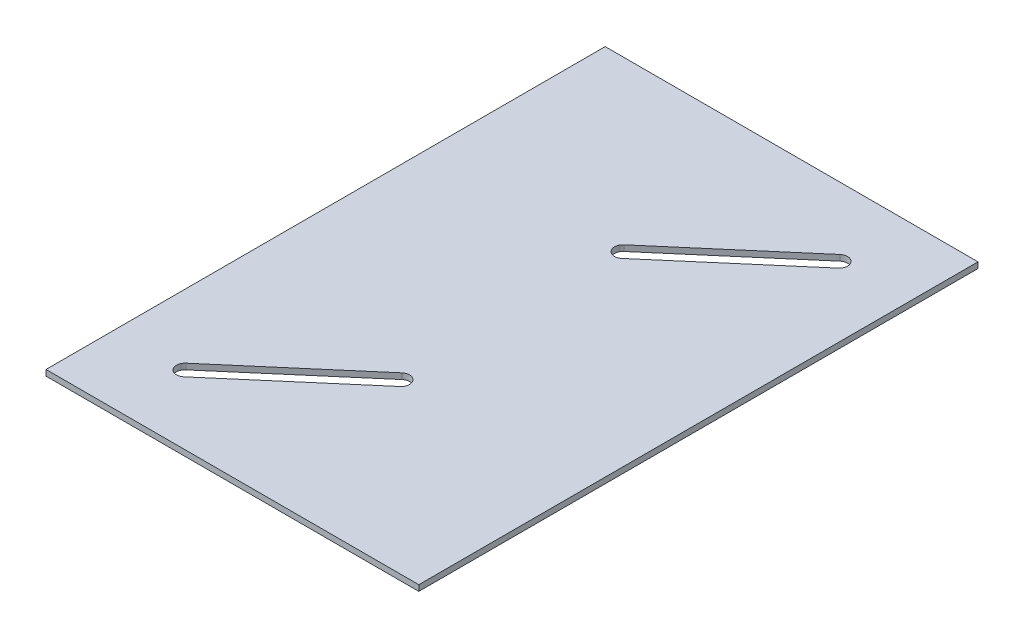
SolidWorks part; units mm, degrees
ref_plane "Front Plane" through (0, 0, 0) normal (0, 0, 1) x (1, 0, 0)
ref_plane "Top Plane" through (0, 0, 0) normal (0, 1, 0) x (1, 0, 0)
ref_plane "Right Plane" through (0, 0, 0) normal (1, 0, 0) x (0, 0, -1)
sketch "Sketch1" plane through (0, 0, 0) normal (0, 1, 0) x (1, 0, 0)
  line L1 (-50.8, -63.5) -> (50.8, -63.5)
  line L2 (-50.8, -63.5) -> (-50.8, 63.5)
  line L3 (-50.8, 63.5) -> (50.8, 63.5)
  line L4 (50.8, -63.5) -> (50.8, 63.5)
  dimension "D1" = 101.6
  dimension "D2" = 127
  dimension "D3" = 50.8
  dimension "D4" = 63.5
extrude "Boss-Extrude1" add sketch "Sketch1" along normal blind 1.5875
sketch "Sketch3" plane through (0, 1.5875, 0) normal (0, 1, 0) x (1, 0, 0)
  line L0 (0, -63.5) -> (0, 63.5) construction
  line L1 (-50.8, -63.5) -> (50.8, -63.5) construction
  line L2 (50.8, 63.5) -> (-50.8, 63.5) construction
  line L3 (0, 30.226) -> (31.75, 57.404) construction
  line L4 (50.8, -63.5) -> (50.8, 63.5) construction
  line L5 (50.8, 0) -> (-50.8, 0) construction
  line L6 (-50.8, 63.5) -> (-50.8, -63.5) construction
  line L7 (-1.4866, 31.9626) -> (30.2634, 59.1406)
  line L8 (1.4866, 28.4894) -> (33.2366, 55.6674)
  line L9 (0, -30.226) -> (-31.75, -57.404) construction
  line L10 (1.4866, -31.9626) -> (-30.2634, -59.1406)
  line L11 (-1.4866, -28.4894) -> (-33.2366, -55.6674)
  arc A0 (-1.4866, 31.9626) -> (1.4866, 28.4894) centre (0, 30.226) ccw
  arc A1 (33.2366, 55.6674) -> (30.2634, 59.1406) centre (31.75, 57.404) ccw
  arc A2 (1.4866, -31.9626) -> (-1.4866, -28.4894) centre (0, -30.226) ccw
  arc A3 (-33.2366, -55.6674) -> (-30.2634, -59.1406) centre (-31.75, -57.404) ccw
  point P15 (15.875, 43.815)
  point P24 (-15.875, -43.815)
  point P29 (0, 0)
  dimension "D1" = 30.226
  dimension "D2" = 27.178
  dimension "D3" = 31.75
  dimension "D4" = 4.572
  dimension "D5" = 2
extrude "Cut-Extrude1" cut sketch "Sketch3" against normal through all
sketch "Sketch4" plane through (0, 1.5875, 0) normal (0, 1, 0) x (1, 0, 0)
  line L0 (-50.8, 63.5) -> (50.8, 63.5)
  line L1 (-50.8, 63.5) -> (-50.8, 76.2)
  line L2 (50.8, 63.5) -> (50.8, 76.2)
  line L3 (-50.8, 76.2) -> (50.8, 76.2)
  line L4 (-50.8, -63.5) -> (50.8, -63.5)
  line L5 (-50.8, -63.5) -> (-50.8, -76.2)
  line L6 (50.8, -63.5) -> (50.8, -76.2)
  line L7 (-50.8, -76.2) -> (50.8, -76.2)
  dimension "D1" = 12.7
  dimension "D2" = 12.7
extrude "Boss-Extrude2" add sketch "Sketch4" against normal blind 1.5875
sketch "Sketch5" plane through (0, 1.5875, 0) normal (0, 1, 0) x (1, 0, 0)
  line L0 (-11.43, 76.2) -> (11.43, 76.2)
  line L1 (-11.43, 76.2) -> (-11.43, 68.58)
  line L2 (11.43, 76.2) -> (11.43, 68.58)
  line L3 (-11.43, 68.58) -> (11.43, 68.58)
  line L4 (50.8, 76.2) -> (-50.8, 76.2) construction
  line L5 (-50.8, 76.2) -> (-50.8, -76.2) construction
  dimension "D1" = 7.62
  dimension "D2" = 22.86
  dimension "D3" = 39.37
sketch "Sketch6" plane through (0, 1.5875, 0) normal (0, 1, 0) x (1, 0, 0)
  circle A0 centre (-11.43, 68.58) radius 0.0127
  circle A1 centre (11.43, 68.58) radius 0.0127
  dimension "D1" = 0.0254
  dimension "D2" = 0.0254
extrude "Cut-Extrude2" cut sketch "Sketch6" against normal through all
